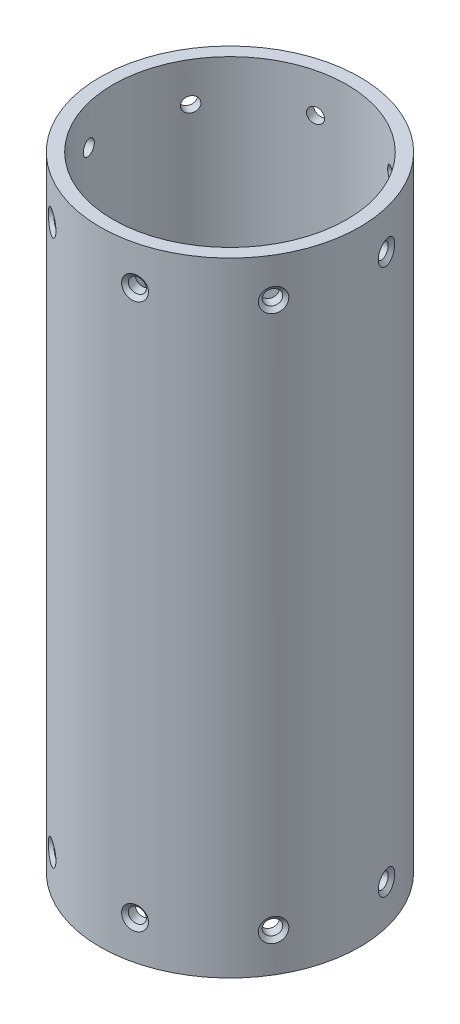
SolidWorks part; units mm, degrees
ref_plane "Front Plane" through (0, 0, 0) normal (0, 0, 1) x (1, 0, 0)
ref_plane "Top Plane" through (0, 0, 0) normal (0, 1, 0) x (1, 0, 0)
ref_plane "Right Plane" through (0, 0, 0) normal (1, 0, 0) x (0, 0, -1)
sketch "Sketch1" plane through (0, 0, 0) normal (0, 1, 0) x (1, 0, 0)
  circle A0 centre (0, 0) radius 31.75
  circle A1 centre (0, 0) radius 28.575
  dimension "D1" = 63.5
  dimension "D2" = 57.15
extrude "Boss-Extrude1" add sketch "Sketch1" along normal blind 152.4
hole_wizard "CSK for #4 Flat Head Machine Screw (100)2" positions "3DSketch2" profile "Sketch4" countersink size "#4" standard "ANSI Inch" end condition up to next
sketch3d "3DSketch2"
  point P0 (-27.1498, 142.875, -16.4606)
  point P10 (0, 0, 0)
  point P11 (0, 0, 0)
  point P12 (0, 0, 0)
  point P13 (0, 0, 0)
  dimension "D1" = 9.525
sketch "Sketch4" plane through (-27.1498, 142.875, -16.4606) normal (0, 1, 0) x (-0.5184, 0, 0.8551)
  line L0 (0, 0) -> (0, 3.175)
  line L1 (0, 3.175) -> (1.8288, 3.175)
  line L2 (1.8288, 3.175) -> (1.8288, 0.8632)
  line L3 (1.8288, 0.8632) -> (2.8575, 0)
  line L5 (2.8575, 0) -> (0, 0)
  line L6 (-1.8288, 0.8632) -> (-2.8575, 0) construction
  line L11 (0, -6.35) -> (0, 107.95) construction
  dimension "Thru Hole Dia." = 3.6576
  dimension "Thru Hole Depth" = 3.175
  dimension "Near C'Sink Dia." = 5.715
  dimension "Near C'Sink Angle" = 100
pattern_circular "CirPattern1" count 8 over 360 about axis through (0, 152.4, 0) along (0, -1, 0) of "CSK for #4 Flat Head Machine Screw (100)2"
pattern_linear "LPattern1" count 2 spacing 133.35 along (0, -1, 0) of "CirPattern1"
